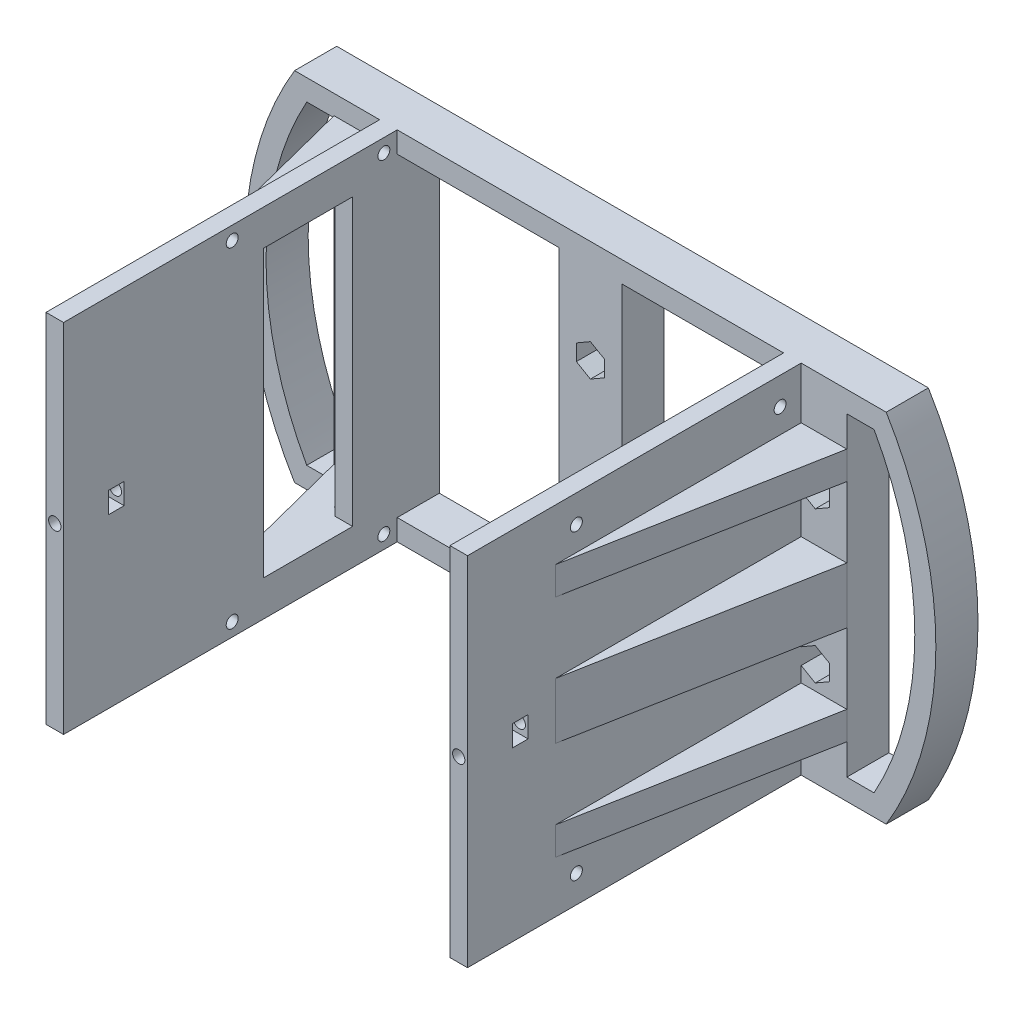
SolidWorks part; units mm, degrees
material "ABS"
ref_plane "Front Plane" through (0, 0, 0) normal (0, 0, 1) x (1, 0, 0)
ref_plane "Top Plane" through (0, 0, 0) normal (0, 1, 0) x (1, 0, 0)
ref_plane "Right Plane" through (0, 0, 0) normal (1, 0, 0) x (0, 0, -1)
sketch "Sketch1" plane through (0, 0, 0) normal (0, 0, 1) x (1, 0, 0)
  line L1 (-76.2, -50.8) -> (76.2, -50.8)
  line L2 (-76.2, -50.8) -> (-76.2, 50.8)
  line L3 (-76.2, 50.8) -> (76.2, 50.8)
  line L4 (76.2, -50.8) -> (76.2, 50.8)
  line L5 (-76.2, -50.8) -> (76.2, 50.8) construction
  line L6 (-76.2, 50.8) -> (76.2, -50.8) construction
  point P0 (0, 0)
  dimension "D1" = 152.4
  dimension "D2" = 101.6
extrude "Boss-Extrude1" add sketch "Sketch1" along normal blind 12
hole_wizard "#6 Clearance Hole1" positions "3DSketch1" profile "Sketch3" hole size "#6" standard "ANSI Inch" end condition through all
sketch3d "3DSketch1"
  line L1 (0, 21.4643, 12) -> (0, 21.4643, 0) construction
  line L2 (0, 21.4643, 0) -> (0, 0, 0) construction
  line L4 (0, 21.4643, 12) -> (0, -21.4643, 12) construction
  point P0 (-64.008, 21.4643, 12)
  point P4 (64.008, 21.4643, 12)
  point P6 (64.008, -21.4643, 12)
  point P8 (-64.008, -21.4643, 12)
  point P16 (0, 21.4643, 12)
  point P18 (0, -21.4643, 12)
  dimension "D1" = 42.9285
  dimension "D2" = 21.4643
  dimension "D3" = 64.008
  dimension "D4" = 64.008
sketch "Sketch3" plane through (-64.008, 21.4643, 12) normal (1, 0, 0) x (0, -1, 0)
  line L0 (0, 0) -> (0, 12)
  line L1 (0, 12) -> (1.8986, 12)
  line L2 (1.8986, 12) -> (1.8986, 0)
  line L5 (1.8986, 0) -> (0, 0)
  line L11 (0, -6.35) -> (0, 107.95) construction
  dimension "Thru Hole Dia." = 3.7973
  dimension "Thru Hole Depth" = 12
sketch "Sketch4" plane through (0, 0, 12) normal (0, 0, 1) x (1, 0, 0)
  line L0 (-76.2, 50.8) -> (-84.2279, 50.8)
  line L1 (-76.2, -50.8) -> (-84.2279, -50.8)
  line L2 (76.2, -50.8) -> (84.2279, -50.8)
  line L3 (76.2, 50.8) -> (84.2279, 50.8)
  line L4 (0, 0) -> (0, 81.4816) construction
  line L5 (76.2, 50.8) -> (76.2, -50.8)
  line L6 (-76.2, 50.8) -> (-76.2, -50.8)
  arc A0 (-84.2279, 50.8) -> (-84.2279, -50.8) centre (0, 0) ccw
  arc A1 (84.2279, 50.8) -> (84.2279, -50.8) centre (0, 0) cw
  dimension "D1" = 98.3615
extrude "Boss-Extrude2" add sketch "Sketch4" against normal up to surface (12 mm away) up to face at (-62.1093, 21.4643, 0)
sketch "Sketch6" plane through (0, 0, 12) normal (0, 0, 1) x (1, 0, 0)
  line L1 (-68.008, 19.1549) -> (-64.008, 16.8455)
  line L2 (-64.008, 16.8455) -> (-60.008, 19.1549)
  line L3 (-60.008, 19.1549) -> (-60.008, 23.7737)
  line L4 (-60.008, 23.7737) -> (-64.008, 26.0831)
  line L5 (-64.008, 26.0831) -> (-68.008, 23.7737)
  line L6 (-68.008, 23.7737) -> (-68.008, 19.1549)
  line L7 (4, 19.1549) -> (4, 23.7737)
  line L8 (4, 23.7737) -> (0, 26.0831)
  line L9 (0, 26.0831) -> (-4, 23.7737)
  line L10 (-4, 23.7737) -> (-4, 19.1549)
  line L11 (-4, 19.1549) -> (0, 16.8455)
  line L12 (0, 16.8455) -> (4, 19.1549)
  line L13 (68.008, 19.1549) -> (68.008, 23.7737)
  line L14 (68.008, 23.7737) -> (64.008, 26.0831)
  line L15 (64.008, 26.0831) -> (60.008, 23.7737)
  line L16 (60.008, 23.7737) -> (60.008, 19.1549)
  line L17 (60.008, 19.1549) -> (64.008, 16.8455)
  line L18 (64.008, 16.8455) -> (68.008, 19.1549)
  line L19 (68.008, -23.7737) -> (68.008, -19.1549)
  line L20 (68.008, -19.1549) -> (64.008, -16.8455)
  line L21 (64.008, -16.8455) -> (60.008, -19.1549)
  line L22 (60.008, -19.1549) -> (60.008, -23.7737)
  line L23 (60.008, -23.7737) -> (64.008, -26.0831)
  line L24 (64.008, -26.0831) -> (68.008, -23.7737)
  line L25 (4, -23.7737) -> (4, -19.1549)
  line L26 (4, -19.1549) -> (0, -16.8455)
  line L27 (0, -16.8455) -> (-4, -19.1549)
  line L28 (-4, -19.1549) -> (-4, -23.7737)
  line L29 (-4, -23.7737) -> (0, -26.0831)
  line L30 (0, -26.0831) -> (4, -23.7737)
  line L31 (-60.008, -23.7737) -> (-60.008, -19.1549)
  line L32 (-60.008, -19.1549) -> (-64.008, -16.8455)
  line L33 (-64.008, -16.8455) -> (-68.008, -19.1549)
  line L34 (-68.008, -19.1549) -> (-68.008, -23.7737)
  line L35 (-68.008, -23.7737) -> (-64.008, -26.0831)
  line L36 (-64.008, -26.0831) -> (-60.008, -23.7737)
  circle A0 centre (-64.008, 21.4643) radius 4 construction
  circle A1 centre (0, 21.4643) radius 4 construction
  circle A2 centre (64.008, 21.4643) radius 4 construction
  circle A3 centre (64.008, -21.4643) radius 4 construction
  circle A4 centre (0, -21.4643) radius 4 construction
  circle A5 centre (-64.008, -21.4643) radius 4 construction
  dimension "D1" = 8
extrude "Cut-Extrude2" cut sketch "Sketch6" against normal blind 9.525
sketch "Sketch5" plane through (0, 0, 12) normal (0, 0, 1) x (1, 0, 0)
  line L4 (-73.008, 44.8) -> (-73.008, -44.8)
  line L5 (73.008, 44.8) -> (73.008, -44.8)
  line L6 (80.7688, 44.8) -> (-80.7688, 44.8)
  line L7 (-80.7688, -44.8) -> (80.7688, -44.8)
  line L8 (80.7688, 44.8) -> (73.008, 44.8)
  line L9 (-80.7688, -44.8) -> (-73.008, -44.8)
  line L10 (73.008, -44.8) -> (80.7688, -44.8)
  line L11 (-73.008, 44.8) -> (-80.7688, 44.8)
  line L12 (-64.008, 21.4643) -> (-64.008, -21.4643) construction
  line L13 (-55.008, 44.8) -> (-9, 44.8)
  line L14 (-55.008, 44.8) -> (-55.008, -44.8)
  line L15 (-55.008, -44.8) -> (-9, -44.8)
  line L16 (-9, 44.8) -> (-9, -44.8)
  line L17 (-55.008, 44.8) -> (-9, -44.8) construction
  line L18 (-55.008, -44.8) -> (-9, 44.8) construction
  line L19 (9, 44.8) -> (55.008, 44.8)
  line L20 (9, 44.8) -> (9, -44.8)
  line L21 (9, -44.8) -> (55.008, -44.8)
  line L22 (55.008, 44.8) -> (55.008, -44.8)
  line L23 (9, 44.8) -> (55.008, -44.8) construction
  line L24 (9, -44.8) -> (55.008, 44.8) construction
  line L25 (0, 21.4643) -> (0, -21.4643) construction
  arc A12 (80.7688, -44.8) -> (80.7688, 44.8) centre (0, 0) ccw
  arc A13 (-80.7688, 44.8) -> (-80.7688, -44.8) centre (0, 0) ccw
  arc A14 (80.7688, -44.8) -> (80.7688, 44.8) centre (0, 0) ccw
  arc A15 (-80.7688, 44.8) -> (-80.7688, -44.8) centre (0, 0) ccw
  point P4 (-32.004, 0)
  point P9 (32.004, 0)
  dimension "D2" = 18
  dimension "D3" = 18
  dimension "D1" = 6
extrude "Cut-Extrude1" cut sketch "Sketch5" against normal through all
sketch "Sketch7" plane through (0, 0, 12) normal (0, 0, 1) x (1, 0, 0)
  line L1 (-60.008, 50.8) -> (-60.008, -50.8)
  line L3 (-60.008, -23.7737) -> (-60.008, -19.1549) construction
  line L5 (-55.008, 50.8) -> (-55.008, -50.8)
  line L6 (84.2279, 50.8) -> (-84.2279, 50.8) construction
  line L7 (-84.2279, -50.8) -> (84.2279, -50.8) construction
  line L8 (-55.008, 44.8) -> (-55.008, -44.8) construction
  line L9 (-55.008, -50.8) -> (-60.008, -50.8)
  line L10 (-55.008, 50.8) -> (-60.008, 50.8)
extrude "Boss-Extrude3" add sketch "Sketch7" along normal blind 50.8
hole_wizard "M3 Clearance Hole1" positions "3DSketch2" profile "Sketch8" hole size "M3" standard "ANSI Metric" end condition through all
sketch3d "3DSketch2"
  line L0 (-55.008, 46.99, 15.81) -> (-55.008, -46.99, 15.81) construction
  line L1 (-55.008, -46.99, 15.81) -> (-55.008, -46.99, 58.99) construction
  line L2 (-55.008, -46.99, 58.99) -> (-55.008, 46.99, 58.99) construction
  line L3 (-55.008, 46.99, 58.99) -> (-55.008, 46.99, 15.81) construction
  line L5 (-55.008, 0, 62.8) -> (-55.008, 0, 58.99) construction
  line L6 (-55.008, -50.8, 62.8) -> (-55.008, 50.8, 62.8) construction
  line L8 (-55.008, 50.8, 37.4) -> (-55.008, 46.99, 37.4) construction
  line L9 (-55.008, 50.8, 62.8) -> (-55.008, 50.8, 12) construction
  point P0 (-55.008, 46.99, 58.99)
  point P2 (-55.008, 46.99, 15.81)
  point P4 (-55.008, -46.99, 15.81)
  point P6 (-55.008, -46.99, 58.99)
  dimension "D1" = 93.98
  dimension "D2" = 43.18
sketch "Sketch8" plane through (-55.008, 46.99, 58.99) normal (0, 1, 0) x (0, 0, -1)
  line L0 (0, 0) -> (0, 43.3535)
  line L1 (0, 43.3535) -> (1.7, 43.3535)
  line L2 (1.7, 43.3535) -> (1.7, 0)
  line L5 (1.7, 0) -> (0, 0)
  line L11 (0, -6.35) -> (0, 107.95) construction
  dimension "Thru Hole Dia." = 3.4
  dimension "Thru Hole Depth" = 43.3535
sketch "Sketch9" plane through (-55.008, 0, 0) normal (1, 0, 0) x (0, 0, -1)
  line L6 (-24.7, -40.64) -> (-50.1, -40.64)
  line L7 (-50.1, -40.64) -> (-50.1, 40.64)
  line L8 (-50.1, 40.64) -> (-24.7, 40.64)
  line L9 (-24.7, 40.64) -> (-24.7, -40.64)
  line L10 (-12, -50.8) -> (-12, -44.8) construction
  line L11 (-62.8, -50.8) -> (-62.8, 50.8) construction
  line L12 (-62.8, -50.8) -> (-12, -50.8) construction
  line L13 (-62.8, 50.8) -> (-12, 50.8) construction
  dimension "D1" = 12.7
  dimension "D2" = 12.7
  dimension "D3" = 10.16
  dimension "D4" = 10.16
extrude "Cut-Extrude3" cut sketch "Sketch9" against normal through all
ref_plane "Plane1" through (-71.4029, 0, 18.2724) normal (0.9688, 0, -0.2479) x (-0.2479, 0, -0.9688)
sketch "Sketch10" plane through (-71.4029, 0, 18.2724) normal (0.9688, 0, -0.2479) x (-0.2479, 0, -0.9688)
  line L0 (-45.9625, 42.965) -> (6.4745, 42.965) construction
  line L1 (-45.9625, 50.8) -> (-45.9625, -50.8) construction
  line L2 (6.4745, -44.8) -> (6.4745, 44.8) construction
  line L3 (-45.9625, -42.965) -> (6.4745, -42.965) construction
  line L5 (-9.0519, 40.64) -> (-33.659, 40.64) construction
  line L6 (-33.659, -40.64) -> (-9.0519, -40.64) construction
  line L7 (-33.659, -40.64) -> (-9.0519, -40.64) construction
  line L8 (-42.2714, 45.29) -> (-42.2714, 42.965) construction
  line L9 (-21.3555, 40.64) -> (-21.3555, 42.965) construction
  line L10 (-21.3555, -40.64) -> (-21.3555, -42.965) construction
  line L11 (-42.2714, -45.29) -> (-42.2714, -42.965) construction
  line L14 (6.4745, 45.29) -> (-45.9625, 45.29)
  line L16 (-45.9625, -40.64) -> (-45.9625, -45.29)
  line L17 (-45.9625, -45.29) -> (6.4745, -45.29)
  line L18 (6.4745, -45.29) -> (6.4745, -40.64)
  line L19 (6.4745, -40.64) -> (-45.9625, -40.64)
  line L20 (-9.0519, 40.64) -> (-33.659, 40.64) construction
  line L21 (6.4745, 40.64) -> (-45.9625, 40.64)
  line L22 (-45.9625, 40.64) -> (-45.9625, 45.29)
  line L23 (6.4745, 45.29) -> (6.4745, 40.64)
  ellipse E0 centre (-42.2714, -46.99) end of major axis (-42.2714, -45.29) minor radius 1.6469 construction
  ellipse E1 centre (-42.2714, -46.99) end of major axis (-42.2714, -45.29) minor radius 1.6469 construction
  ellipse E2 centre (-42.2714, 46.99) end of major axis (-42.2714, 48.69) minor radius 1.6469 construction
  ellipse E3 centre (-42.2714, 46.99) end of major axis (-42.2714, 48.69) minor radius 1.6469 construction
extrude "Boss-Extrude4" add sketch "Sketch10" along normal up to surface (13.4189 mm away) up to face at (-60.008, 0, 37.4)
sketch "Sketch11" plane through (0, -45.29, 0) normal (0, -1, 0) x (-1, 0, 0)
  line L0 (64.508, -18.81) -> (62.258, -22.7071)
  line L2 (62.258, -22.7071) -> (60.008, -18.81)
  line L3 (60.008, -18.81) -> (60.008, -12.81)
  line L5 (60.008, -12.81) -> (64.508, -12.81)
  line L6 (64.508, -12.81) -> (64.508, -18.81)
  line L7 (60.008, -55.99) -> (64.508, -55.99)
  line L8 (64.508, -55.99) -> (64.508, -61.99)
  line L9 (64.508, -61.99) -> (60.008, -61.99) construction
  line L10 (60.008, -61.99) -> (60.008, -55.99)
  line L11 (60.008, -17.51) -> (60.008, -14.11) construction
  line L12 (60.008, -17.51) -> (60.008, -14.11) construction
  line L14 (60.008, -60.69) -> (60.008, -57.29) construction
  line L15 (60.008, -60.69) -> (60.008, -57.29) construction
  line L17 (60.008, -61.99) -> (60.008, -62.8)
  line L18 (60.008, -62.8) -> (64.508, -62.8)
  line L19 (64.508, -62.8) -> (64.508, -61.99)
  point P2 (60.008, -15.81)
  point P3 (60.008, -58.99)
  dimension "D1" = 6
  dimension "D2" = 4.5
  dimension "D3" = 60
  dimension "D4" = 6
extrude "Cut-Extrude4" cut sketch "Sketch11" against normal through all
sketch "Sketch12" plane through (0, 0, 12) normal (0, 0, 1) x (1, 0, 0)
  line L9 (60.008, 50.8) -> (60.008, -50.8)
  line L10 (84.2279, 50.8) -> (-55.008, 50.8) construction
  line L11 (-55.008, -50.8) -> (84.2279, -50.8) construction
  line L12 (60.008, -50.8) -> (55.008, -50.8)
  line L13 (55.008, -50.8) -> (55.008, 50.8)
  line L14 (55.008, 50.8) -> (60.008, 50.8)
  line L15 (55.008, -44.8) -> (55.008, 44.8) construction
  line L16 (60.008, 23.7737) -> (60.008, 19.1549) construction
extrude "Boss-Extrude5" add sketch "Sketch12" along normal blind 70
hole_wizard "M3 Clearance Hole2" positions "3DSketch3" profile "Sketch13" hole size "M3" standard "ANSI Metric" end condition through all
sketch3d "3DSketch3"
  line L0 (55.008, 43, 18) -> (55.008, -43, 18) construction
  line L1 (55.008, -43, 18) -> (55.008, -43, 76) construction
  line L2 (55.008, -43, 76) -> (55.008, 43, 76) construction
  line L3 (55.008, 43, 76) -> (55.008, 43, 18) construction
  line L5 (55.008, 43, 47) -> (55.008, 50.8, 47) construction
  line L6 (55.008, 50.8, 82) -> (55.008, 50.8, 12) construction
  line L8 (55.008, 0, 76) -> (55.008, 0, 82) construction
  line L9 (55.008, 50.8, 82) -> (55.008, -50.8, 82) construction
  point P0 (55.008, -43, 76)
  point P2 (55.008, -43, 18)
  point P4 (55.008, 43, 18)
  point P6 (55.008, 43, 76)
  dimension "D1" = 58
  dimension "D2" = 86
sketch "Sketch13" plane through (55.008, -43, 76) normal (0, 1, 0) x (0, 0, 1)
  line L0 (0, 0) -> (0, 43.3535)
  line L1 (0, 43.3535) -> (1.7, 43.3535)
  line L2 (1.7, 43.3535) -> (1.7, 0)
  line L5 (1.7, 0) -> (0, 0)
  line L11 (0, -6.35) -> (0, 107.95) construction
  dimension "Thru Hole Dia." = 3.4
  dimension "Thru Hole Depth" = 43.3535
ref_plane "Plane2" through (72.7282, 0, 13.5067) normal (-0.9832, 0, -0.1826) x (-0.1826, 0, 0.9832)
sketch "Sketch14" plane through (72.7282, 0, 13.5067) normal (-0.9832, 0, -0.1826) x (-0.1826, 0, 0.9832)
  line L0 (69.6645, -8) -> (-1.5324, -8)
  line L1 (69.6645, -50.8) -> (69.6645, 50.8) construction
  line L2 (-1.5324, 44.8) -> (-1.5324, -44.8) construction
  line L3 (-1.5324, -8) -> (-1.5324, 8)
  line L4 (-1.5324, 8) -> (69.6645, 8)
  line L5 (69.6645, 8) -> (69.6645, -8)
  line L6 (69.6645, 0) -> (-1.5324, 0) construction
  line L7 (0.1109, -26.0831) -> (-0.6195, -23.7737) construction
  line L8 (0.1109, -26.0831) -> (-0.6195, -23.7737) construction
  line L9 (-1.5324, -28.0831) -> (69.6645, -28.0831)
  line L10 (69.6645, -28.0831) -> (69.6645, -36.0831)
  line L11 (69.6645, -36.0831) -> (-1.5324, -36.0831)
  line L12 (-1.5324, -36.0831) -> (-1.5324, -28.0831)
  line L13 (0.1109, -26.0831) -> (0.1109, -28.0831) construction
  line L14 (-1.5324, 36.0831) -> (-1.5324, 28.0831)
  line L15 (-1.5324, 28.0831) -> (69.6645, 28.0831)
  line L16 (69.6645, 36.0831) -> (-1.5324, 36.0831)
  line L17 (69.6645, 28.0831) -> (69.6645, 36.0831)
  point P12 (-1.5324, 0)
  dimension "D1" = 16
  dimension "D2" = 2
  dimension "D3" = 8
extrude "Boss-Extrude6" add sketch "Sketch14" along normal up to surface up to face at (60.008, -43, 77.7)
sketch "Sketch15" plane through (0, 0, 82) normal (0, 0, 1) x (1, 0, 0)
  line L10 (60.008, 50.8) -> (55.008, 50.8)
  line L11 (55.008, 50.8) -> (55.008, -50.8)
  line L12 (55.008, -50.8) -> (60.008, -50.8)
  line L13 (60.008, -50.8) -> (60.008, -36.0831)
  line L14 (60.008, -36.0831) -> (60.008, -28.0831)
  line L15 (60.008, -28.0831) -> (60.008, -8)
  line L16 (60.008, -8) -> (60.008, 8)
  line L17 (60.008, 8) -> (60.008, 28.0831)
  line L18 (60.008, 28.0831) -> (60.008, 36.0831)
  line L19 (60.008, 36.0831) -> (60.008, 50.8)
  line L20 (60.008, 50.8) -> (55.008, 50.8)
  line L21 (55.008, 50.8) -> (55.008, -50.8)
  line L22 (55.008, -50.8) -> (60.008, -50.8)
  line L23 (60.008, -50.8) -> (60.008, -36.0831)
  line L24 (60.008, -36.0831) -> (60.008, -28.0831)
  line L25 (60.008, -28.0831) -> (60.008, -8)
  line L26 (60.008, -8) -> (60.008, 8)
  line L27 (60.008, 8) -> (60.008, 28.0831)
  line L28 (60.008, 28.0831) -> (60.008, 36.0831)
  line L29 (60.008, 36.0831) -> (60.008, 50.8)
  dimension "D1" = 0
extrude "Boss-Extrude7" add sketch "Sketch15" along normal blind 25
sketch "Sketch16" plane through (0, 0, 107) normal (0, 0, 1) x (1, 0, 0)
  line L4 (-55.008, 50.8) -> (-60.008, 50.8)
  line L5 (-60.008, 50.8) -> (-60.008, -50.8)
  line L6 (-60.008, -50.8) -> (-55.008, -50.8)
  line L7 (-55.008, -50.8) -> (-55.008, 50.8)
  line L8 (-55.008, 50.8) -> (-60.008, 50.8)
  line L9 (-60.008, 50.8) -> (-60.008, -50.8)
  line L10 (-60.008, -50.8) -> (-55.008, -50.8)
  line L11 (-55.008, -50.8) -> (-55.008, 50.8)
  dimension "D1" = 0
extrude "Boss-Extrude8" add sketch "Sketch16" against normal up to next
sketch "Sketch17" plane through (0, 0, 107) normal (0, 0, 1) x (1, 0, 0)
  line L0 (-42.7128, 0) -> (41.7274, 0) construction
  line L1 (-60.008, 0) -> (-55.008, 0) construction
  line L2 (-60.008, 50.8) -> (-60.008, -50.8) construction
  line L3 (-55.008, -50.8) -> (-55.008, 50.8) construction
  line L4 (55.008, 0) -> (60.008, 0) construction
  line L5 (55.008, 50.8) -> (55.008, -50.8) construction
  line L6 (60.008, -50.8) -> (60.008, 50.8) construction
  circle A0 centre (-57.508, 0) radius 1.75
  circle A1 centre (57.508, 0) radius 1.75
  point P15 (-57.508, 0)
  point P16 (57.508, 0)
  dimension "D1" = 3.5
extrude "Cut-Extrude5" cut sketch "Sketch17" against normal blind 20
sketch "Sketch19" plane through (-60.008, 0, 0) normal (-1, 0, 0) x (0, 0, 1)
  line L0 (92, 50.8) -> (92, -50.8) construction
  line L1 (107, 50.8) -> (12, 50.8) construction
  line L2 (107, -50.8) -> (12, -50.8) construction
  line L3 (107, 50.8) -> (107, -50.8) construction
  line L5 (89.75, -3) -> (94.25, -3)
  line L6 (89.75, -3) -> (89.75, 3)
  line L7 (89.75, 3) -> (94.25, 3)
  line L8 (94.25, -3) -> (94.25, 3)
  line L9 (89.75, -3) -> (94.25, 3) construction
  line L10 (89.75, 3) -> (94.25, -3) construction
  point P8 (92, 0)
  point P13 (92, 0)
  dimension "D1" = 15
  dimension "D2" = 6
  dimension "D3" = 4.5
extrude "Cut-Extrude6" cut sketch "Sketch19" against normal through all both and the other way through all
